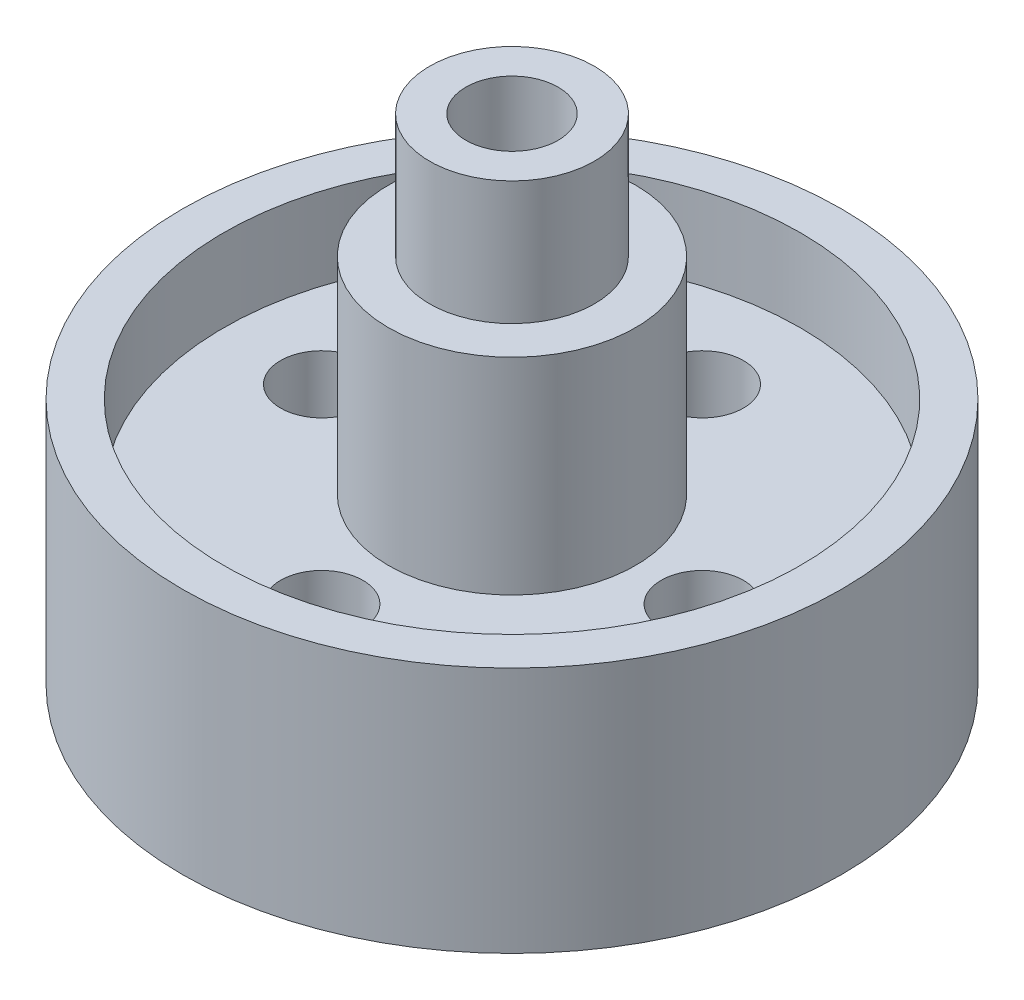
SolidWorks part; units mm, degrees
material "Plain Carbon Steel"
ref_plane "Front Plane" through (0, 0, 0) normal (0, 0, 1) x (1, 0, 0)
ref_plane "Top Plane" through (0, 0, 0) normal (0, 1, 0) x (1, 0, 0)
ref_plane "Right Plane" through (0, 0, 0) normal (1, 0, 0) x (0, 0, -1)
sketch "Sketch1" plane through (0, 0, 0) normal (0, 1, 0) x (1, 0, 0)
  line L0 (0, -61.0693) -> (0, 57.6529) construction
  line L1 (-61.6672, 0) -> (82.3368, 0) construction
  circle A0 centre (0, 0) radius 7.112
  circle A1 centre (0, 0) radius 12.7
  circle A2 centre (0, 0) radius 19.05
  circle A3 centre (0, 0) radius 29.337
  circle A4 centre (0, 0) radius 44.45
  circle A5 centre (0, 0) radius 50.8
  circle A6 centre (0, 29.337) radius 6.35
  circle A7 centre (29.337, 0) radius 6.35
  circle A8 centre (0, -29.337) radius 6.35
  circle A9 centre (-29.337, 0) radius 6.35
  dimension "D1" = 58.674
  dimension "D2" = 101.6
  dimension "D3" = 88.9
  dimension "D4" = 14.224
  dimension "D5" = 25.4
  dimension "D6" = 38.1
  dimension "D7" = 12.7
extrude "Boss-Extrude1" add sketch "Sketch1" along normal blind 38.1 contours A5 A4 region at (-49.3632, 0, 0)
extrude "Boss-Extrude3" add sketch "Sketch1<4>" along normal blind 25.4 contours A4 A9 A3 A6 A7 A8 | A9 A3 A8 A7 A6 A2 region at (22.1767, 0, 0) region at (-43.1928, 0, 0)
sketch "Sketch1<4>" plane through (0, 0, 0) normal (0, 1, 0) x (1, 0, 0) same geometry as "Sketch1"
extrude "Boss-Extrude4" add sketch "Sketch1<5>" along normal blind 57.15 contours A2 A1 region at (-18.5112, 0, 0)
sketch "Sketch1<5>" plane through (0, 0, 0) normal (0, 1, 0) x (1, 0, 0) same geometry as "Sketch1"
extrude "Boss-Extrude5" add sketch "Sketch1<6>" along normal blind 76.2 contours A1 A0 region at (-12.3408, 0, 0)
sketch "Sketch1<6>" plane through (0, 0, 0) normal (0, 1, 0) x (1, 0, 0) same geometry as "Sketch1"
